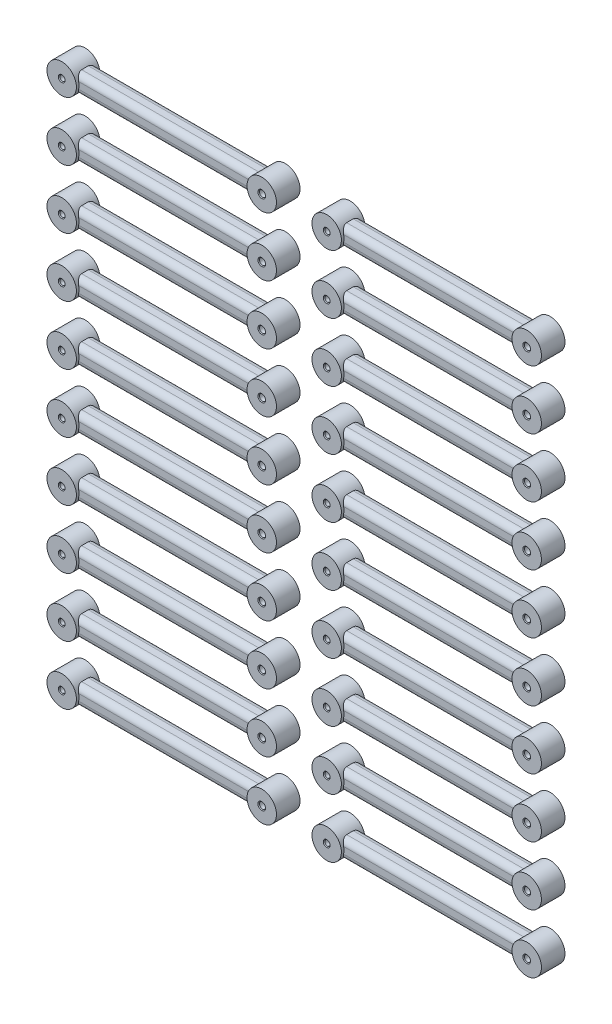
SolidWorks part; units mm, degrees
material "PA 类型 6"
ref_plane "前视基准面" through (0, 0, 0) normal (0, 0, 1) x (1, 0, 0)
ref_plane "上视基准面" through (0, 0, 0) normal (0, 1, 0) x (1, 0, 0)
ref_plane "右视基准面" through (0, 0, 0) normal (1, 0, 0) x (0, 0, -1)
sketch "草图1" plane through (0, 0, 0) normal (0, 0, 1) x (1, 0, 0)
  circle A0 centre (0, 0) radius 2
  circle A1 centre (27.1807, 0) radius 2
  circle A2 centre (0, 0) radius 0.36
  circle A3 centre (27.1807, 0) radius 0.42
  dimension "D1" = 4
  dimension "D2" = 4
  dimension "D3" = 0.84
  dimension "D4" = 0.72
  dimension "D5" = 27.1807
extrude "凸台-拉伸1" add sketch "草图1" along normal mid plane 3.2
ref_plane "基准面1" through (3, 0, 0) normal (1, 0, 0) x (0, 0, -1)
sketch "草图2" plane through (3, 0, 0) normal (1, 0, 0) x (0, 0, -1)
  line L1 (-1.25, -1.25) -> (1.25, -1.25)
  line L2 (-1.25, -1.25) -> (-1.25, 1.25)
  line L3 (-1.25, 1.25) -> (1.25, 1.25)
  line L4 (1.25, -1.25) -> (1.25, 1.25)
  line L5 (-1.25, -1.25) -> (1.25, 1.25) construction
  line L6 (-1.25, 1.25) -> (1.25, -1.25) construction
  point P0 (0, 0)
  dimension "D1" = 2.5
extrude "凸台-拉伸2" add sketch "草图2" along normal up to surface and the other way up to surface contours L1 L4 L3 L2 region at (3, 0, 0) up to face at (29.1807, 0, 1.6) other way up to face at (2, 0, 1.6)
chamfer "倒角1" distance 0.1 angle 45 4 edges at (27.6007, 0, 1.6) (27.6007, 0, -1.6) (0.36, 0, 1.6) (0.36, 0, -1.6)
fillet "圆角1" radius 0.8 4 edges at (13.5904, -1.25, 1.25) (13.5904, -1.25, -1.25) (13.5904, 1.25, 1.25) (13.5904, 1.25, -1.25)
pattern_linear "阵列(线性)1" count 10 spacing 8 along (0, 1, 0) count 2 spacing 36 along (1, 0, 0) of bodies 108
